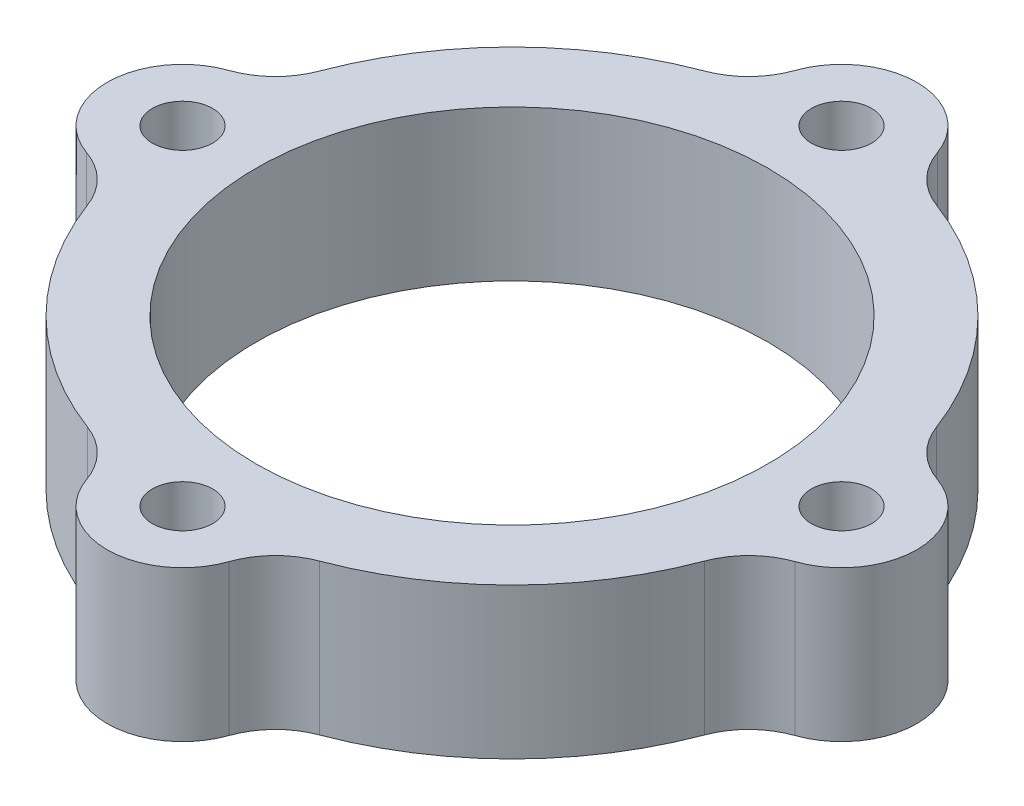
SolidWorks part; units mm, degrees
material "ﾎﾟﾘｴｽﾃﾙ樹脂"
ref_plane "正面" through (0, 0, 0) normal (0, 0, 1) x (1, 0, 0)
ref_plane "平面" through (0, 0, 0) normal (0, 1, 0) x (1, 0, 0)
ref_plane "右側面" through (0, 0, 0) normal (1, 0, 0) x (0, 0, -1)
sketch "ｽｹｯﾁ1" plane through (0, 0, 0) normal (0, 1, 0) x (1, 0, 0)
  circle A0 centre (0, 0) radius 17.5
  circle A1 centre (0, 0) radius 13.6
  circle A2 centre (0, 17.5) radius 4
  circle A3 centre (0, 17.5) radius 1.6
  circle A4 centre (17.5, 0) radius 4
  circle A5 centre (17.5, 0) radius 1.6
  circle A6 centre (0, -17.5) radius 4
  circle A7 centre (0, -17.5) radius 1.6
  circle A8 centre (-17.5, 0) radius 4
  circle A9 centre (-17.5, 0) radius 1.6
  point P19 (0, 0)
  dimension "D2" = 35
  dimension "D3" = 27.2
  dimension "D4" = 3.2
  dimension "D5" = 8
  dimension "D1" = 4
extrude "ﾎﾞｽ - 押し出し1" add sketch "ｽｹｯﾁ1" along normal blind 8 contours A9 A0 A8 A1 | A9 A0 A8 | A8 A0 A6 A1 | A8 A1 A2 A0 | A6 A0 A4 A1 | A7 A0 A6 A1 | A7 A0 A6 | A4 A0 A2 A1 | A5 A0 A4 | A5 A0 A4 A1 | A3 A0 A2 | A3 A0 A2 A1 region at (15.5187, 0, 0) region at (19.2871, 0, 0) region at (10.3733, 0, -10.3733) region at (10.3733, 0, 10.3733) region at (0, 0, -15.5187) region at (0, 0, -19.2871) region at (0, 0, 19.2871) region at (0, 0, 15.5187) region at (-10.3733, 0, -10.3733) region at (-10.3733, 0, 10.3733) region at (-15.5187, 0, 0) region at (-19.2871, 0, 0)
fillet "ﾌｨﾚｯﾄ1" radius 4 8 edges at (-17.0429, 4, 3.9738) (-3.9738, 4, 17.0429) (3.9738, 4, 17.0429) (17.0429, 4, 3.9738) (17.0429, 4, -3.9738) (3.9738, 4, -17.0429) (-17.0429, 4, -3.9738) (-3.9738, 4, -17.0429)
ref_axis "軸1" through (0, 8, 0) along (0, -1, 0)
